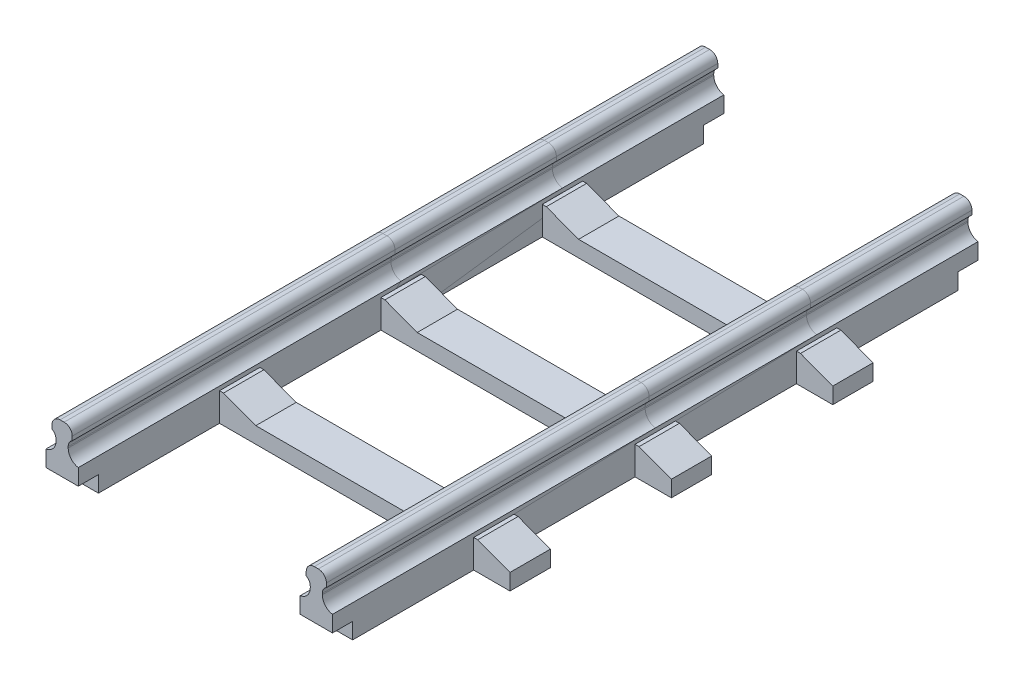
SolidWorks part; units mm, degrees
other "标注1"
sketch "草图3" plane through (-22.25, 4, -10) normal (-0.231, 0.6469, -0.7268) x (-0.9696, -0.2151, 0.1167)
other "标注2"
sketch "草图4" plane through (22.25, 8, -30) normal (0.0083, 0.0567, -0.9984) x (-0.9991, 0.0415, -0.0059)
ref_plane "前视基准面" through (0, 0, 0) normal (0, 0, 1) x (1, 0, 0)
ref_plane "上视基准面" through (0, 0, 0) normal (0, 1, 0) x (1, 0, 0)
ref_plane "右视基准面" through (0, 0, 0) normal (1, 0, 0) x (0, 0, -1)
other "Configuration Table"
sketch "草图1" plane through (0, 0, 0) normal (0, 1, 0) x (1, 0, 0)
  line L0 (-13.75, 11.25) -> (-13.75, -11.25)
  line L13 (-17.75, -11.25) -> (17.75, -11.25)
  line L21 (-17.75, -11.25) -> (-17.75, 11.25)
  line L22 (-17.75, 11.25) -> (17.75, 11.25)
  line L23 (17.75, -11.25) -> (17.75, 11.25)
  line L24 (-17.75, -11.25) -> (17.75, 11.25) construction
  line L25 (-17.75, 11.25) -> (17.75, -11.25) construction
  line L27 (13.75, 11.25) -> (13.75, -11.25)
  line L29 (-13.75, 0) -> (13.75, 0) construction
  line L32 (-22.25, 11.25) -> (22.25, 11.25)
  line L33 (-22.25, 11.25) -> (-22.25, 6.25)
  line L34 (-22.25, 6.25) -> (22.25, 6.25)
  line L35 (22.25, 11.25) -> (22.25, 6.25)
  point P0 (0, 0)
  point P15 (0, 6.25)
  dimension "D3" = 27.5
  dimension "D4" = 5
  dimension "D1" = 35.5
  dimension "D2" = 22.5
  dimension "D5" = 44.5
extrude "凸台-拉伸1" add sketch "草图1" along normal blind 4 contours L34 L21 L13 L0 | L34 L27 L13 L23 | L27 L34 L23 L22 | L21 L34 L0 L22 region at (-15.75, 0, -8.75) region at (-15.75, 0, 2.5) region at (15.75, 0, -8.75) region at (15.75, 0, 2.5)
extrude "凸台-拉伸2" add sketch "草图1<7>" along normal blind 3.5 contours L34 L35 L32 L33
sketch "草图1<7>" plane through (0, 0, 0) normal (0, 1, 0) x (1, 0, 0) same geometry as "草图1"
sketch "草图2" plane through (0, 0, -11.25) normal (0, 0, -1) x (-1, 0, 0)
  line L0 (18.25, 3.5) -> (22.25, 2)
  line L1 (22.25, 3.5) -> (18.25, 3.5)
  line L2 (22.25, 3.5) -> (22.25, 2)
  line L3 (22.25, 2) -> (18.25, 2) construction
  line L4 (18.25, 3.5) -> (18.25, 2) construction
  line L5 (-22.25, 2) -> (-18.25, 3.5)
  line L6 (-22.25, 3.5) -> (-18.25, 3.5)
  line L7 (-22.25, 3.5) -> (-22.25, 2)
  line L8 (-22.25, 2) -> (-18.25, 2) construction
  line L9 (-18.25, 3.5) -> (-18.25, 2) construction
  line L10 (13.75, 3.5) -> (-13.75, 3.5) construction
  line L11 (-13.25, 3.5) -> (-9.25, 3.5)
  line L12 (-13.25, 3.5) -> (-13.25, 2) construction
  line L13 (-13.25, 2) -> (-9.25, 2) construction
  line L14 (-9.25, 3.5) -> (-9.25, 2)
  line L15 (-13.75, 3.5) -> (-13.25, 3.5) construction
  line L16 (13.25, 3.5) -> (9.25, 3.5)
  line L17 (13.25, 3.5) -> (13.25, 2) construction
  line L18 (13.25, 2) -> (9.25, 2) construction
  line L19 (9.25, 3.5) -> (9.25, 2)
  line L20 (13.25, 3.5) -> (13.75, 3.5) construction
  line L21 (17.75, 3.5) -> (18.25, 3.5) construction
  line L22 (-13.25, 3.5) -> (-9.25, 2)
  line L23 (9.25, 2) -> (13.25, 3.5)
  line L24 (-9.25, 2) -> (9.25, 2)
  line L25 (-9.25, 3.5) -> (9.25, 3.5)
  line L26 (-15.75, 4) -> (-15.75, 6.5) construction
  line L27 (14.5, 8) -> (17, 8)
  line L28 (14.5, 8) -> (14.5, 6.5)
  line L29 (14.5, 6.5) -> (17, 6.5)
  line L30 (17, 8) -> (17, 6.5)
  line L31 (-17, 8) -> (-14.5, 8)
  line L32 (-17, 8) -> (-17, 6.5)
  line L33 (-17, 6.5) -> (-14.5, 6.5)
  line L34 (-14.5, 8) -> (-14.5, 6.5)
  line L35 (-13.75, 4) -> (-17.75, 4) construction
  line L36 (15.75, 6.5) -> (15.75, 4) construction
  line L37 (17.75, 4) -> (13.75, 4) construction
  line L38 (15, 6.5) -> (15, 4)
  line L39 (16.5, 6.5) -> (16.5, 4)
  line L40 (16.5, 4) -> (15.75, 4)
  line L41 (15.75, 4) -> (15, 4)
  line L42 (-16.5, 6.5) -> (-16.5, 4)
  line L43 (-16.5, 4) -> (-15.75, 4)
  line L44 (-15.75, 4) -> (-15, 4)
  line L45 (-15, 4) -> (-15, 6.5)
  line M9 (22.25, 3.5) -> (17.75, 3.5)
  line M11 (17.75, 4) -> (13.75, 4)
  line M13 (13.75, 3.5) -> (-13.75, 3.5)
  line M15 (-13.75, 4) -> (-17.75, 4)
  line M17 (-17.75, 3.5) -> (-22.25, 3.5)
  line M18 (-22.25, 3.5) -> (-22.25, 0)
  line M20 (22.25, 0) -> (22.25, 3.5)
  dimension "D1" = 4
  dimension "D2" = 1.5
  dimension "D3" = 2.5
  dimension "D4" = 1.5
  dimension "D5" = 2.5
  dimension "D6" = 1.5
extrude "切除-拉伸1" cut sketch "草图2" against normal through all contours L14 L24 L19 M13 | L19 L23 M13 | L22 L14 M13 | L5 M18 M17 | L0 M9 M20 region at (-20.9167, 3, -11.25) region at (20.9167, 3, -11.25) region at (10.5833, 3, -11.25) region at (0, 2.75, -11.25) region at (-10.5833, 3, -11.25)
extrude "凸台-拉伸4" add sketch "草图2<3>" against normal through all contours L34 L31 L32 L33 | L45 L33 L42 M15 | L30 L27 L28 L29 | L39 L29 L38 M11 region at (-15.75, 7.25, -11.25) region at (-15.75, 5.25, -11.25) region at (15.75, 7.25, -11.25) region at (15.75, 5.25, -11.25)
sketch "草图2<3>" plane through (0, 0, -11.25) normal (0, 0, -1) x (-1, 0, 0) same geometry as "草图2"
fillet "圆角1" radius 1 4 edges at (-16.5, 6.5, 0) (-15, 6.5, 0) (15, 6.5, 0) (16.5, 6.5, 0)
fillet "圆角2" radius 1.5 4 edges at (16.5, 4, 0) (15, 4, 0) (-15, 4, 0) (-16.5, 4, 0)
fillet "圆角3" radius 1 4 edges at (-17, 8, 0) (14.5, 8, 0) (17, 8, 0) (-14.5, 8, 0)
sketch "草图5" plane through (17.75, 0, 0) normal (1, 0, 0) x (0, 0, -1)
  line L0 (-11.25, 4) -> (-11.25, 0) construction
  line L1 (-11.25, 2) -> (-8.75, 2)
  line L2 (-11.25, 2) -> (-11.25, 0)
  line L3 (-11.25, 0) -> (-8.75, 0)
  line L4 (-8.75, 2) -> (-8.75, 0)
  line L5 (-11.25, 0) -> (6.25, 0) construction
  dimension "D1" = 2.5
  dimension "D2" = 2
extrude "切除-拉伸2" cut sketch "草图5" against normal through all
sketch "草图10" plane through (0, 2, 0) normal (0, -1, 0) x (1, 0, 0)
  line L0 (13.75, 11.25) -> (17.75, 8.75) construction
  line L1 (13.75, 11.25) -> (17.75, 11.25) construction
  line L2 (13.75, 8.75) -> (13.75, 11.25) construction
  line L3 (13.75, 8.75) -> (17.75, 8.75) construction
  line L4 (17.75, 8.75) -> (17.75, 11.25) construction
  line L5 (-17.75, 11.25) -> (-13.75, 8.75) construction
  line L6 (-17.75, 11.25) -> (-17.75, 8.75) construction
  line L7 (-17.75, 11.25) -> (-13.75, 11.25) construction
  line L8 (-13.75, -6.25) -> (-13.75, 8.75) construction
  line L9 (-17.75, 8.75) -> (-13.75, 8.75) construction
  circle A0 centre (15.75, 10) radius 0.4
  circle A1 centre (-15.75, 10) radius 0.4
  dimension "D1" = 0.8
extrude "切除-拉伸3" cut sketch "草图10" against normal blind 2
sketch "草图8" plane through (22.25, 0, 0) normal (1, 0, 0) x (0, 0, -1)
  line L0 (8.75, 0) -> (8.75, 18.5305)
  line L1 (11.25, 0) -> (6.25, 0) construction
ref_plane "基准面1" through (0, 0, -8.75) normal (0, 0, -1) x (-1, 0, 0)
mirror "镜向1" about plane through (0, 0, -8.75) normal (0, 0, -1) of bodies 202 196
pattern_linear "阵列(线性)2" count 3 spacing 20 along (0, 0, -1) of bodies 197 192
